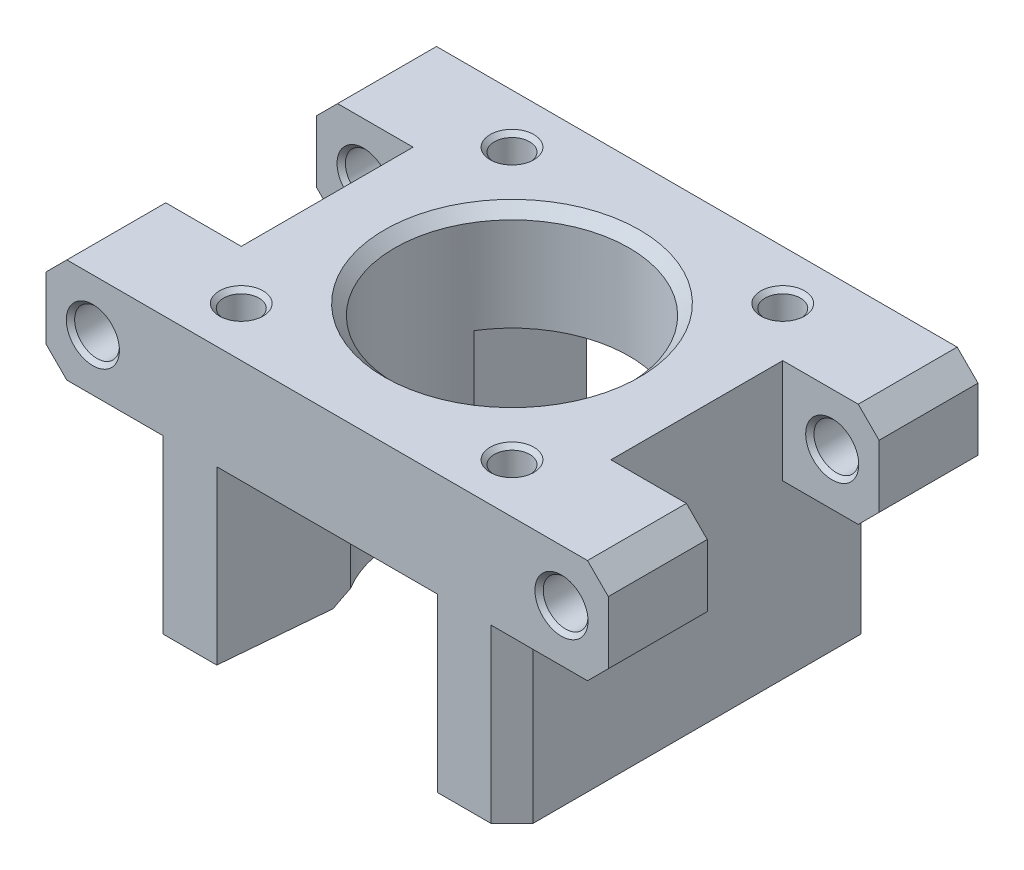
SolidWorks part; units mm, degrees
ref_plane "Top Plane" through (0, 0, 0) normal (0, 0, 1) x (1, 0, 0)
ref_plane "Front Plane" through (0, 0, 0) normal (0, 1, 0) x (1, 0, 0)
ref_plane "Right Plane" through (0, 0, 0) normal (1, 0, 0) x (0, 0, -1)
sketch "Sketch1" plane through (0, 0, 0) normal (0, 0, 1) x (1, 0, 0)
  line L0 (0, 0) -> (0, -10)
  line L1 (0, -10) -> (9.25, -10)
  line L2 (9.25, -10) -> (9.25, -26.5)
  line L3 (9.25, -26.5) -> (44.75, -26.5)
  line L4 (44.75, -26.5) -> (44.75, -10)
  line L5 (44.75, -10) -> (54, -10)
  line L6 (54, -10) -> (54, 0)
  line L7 (54, 0) -> (0, 0)
  dimension "D1" = 54
  dimension "D2" = 10
  dimension "D3" = 16.5
  dimension "D4" = 35.5
  dimension "D5" = 9.25
extrude "Boss-Extrude1" add sketch "Sketch1" along normal blind 35.5
sketch "Sketch2" plane through (0, 0, 35.5) normal (0, 0, 1) x (1, 0, 0)
  line L0 (54, 0) -> (0, 0) construction
  line L1 (0, 0) -> (0, -10) construction
  line L2 (54, -10) -> (54, 0) construction
  circle A0 centre (4.5, -5) radius 2.15
  circle A1 centre (49.5, -5) radius 2.15
  dimension "D1" = 4.3
  dimension "D2" = 4.3
  dimension "D3" = 5
  dimension "D4" = 4.5
  dimension "D5" = 5
  dimension "D6" = 4.5
extrude "Cut-Extrude1" cut sketch "Sketch2" against normal blind 35.5
sketch "Sketch3" plane through (0, -26.5, 0) normal (0, -1, 0) x (1, 0, 0)
  line L0 (9.25, 35.5) -> (9.25, 0) construction
  line L1 (9.25, 0) -> (44.75, 0) construction
  circle A0 centre (27, 17.75) radius 11.25
  dimension "D1" = 22.5
  dimension "D2" = 17.75
  dimension "D3" = 17.75
extrude "Cut-Extrude2" cut sketch "Sketch3" against normal blind 35.5
sketch "Sketch4" plane through (0, -26.5, 0) normal (0, -1, 0) x (1, 0, 0)
  line L1 (40, 4.75) -> (14, 4.75)
  line L2 (40, 4.75) -> (40, 30.75)
  line L3 (40, 30.75) -> (14, 30.75)
  line L4 (14, 4.75) -> (14, 30.75)
  line L5 (40, 4.75) -> (14, 30.75) construction
  line L6 (40, 30.75) -> (14, 4.75) construction
  point P0 (27, 17.75)
  dimension "D1" = 26
  dimension "D2" = 26
hole_wizard "M3 Clearance Hole1" positions "Sketch5" profile "Sketch7" hole size "M3" standard "DIN" end condition through all
sketch "Sketch5" plane through (0, -26.5, 0) normal (0, -1, 0) x (-1, 0, 0)
  point P0 (-14, -30.75)
  point P3 (-40, -30.75)
  point P6 (-40, -4.75)
  point P9 (-14, -4.75)
sketch "Sketch7" plane through (14, -26.5, 30.75) normal (1, 0, 0) x (0, 0, -1)
  line L0 (0, 0) -> (0, 26.5)
  line L1 (0, 26.5) -> (1.7, 26.5)
  line L2 (1.7, 26.5) -> (1.7, 0)
  line L5 (1.7, 0) -> (0, 0)
  line L11 (0, -6.35) -> (0, 107.95) construction
  dimension "Thru Hole Dia." = 3.4
  dimension "Thru Hole Depth" = 26.5
sketch "Sketch8" plane through (0, -26.5, 0) normal (0, -1, 0) x (1, 0, 0)
  line L0 (9.25, 35.5) -> (44.75, 35.5) construction
  line L1 (17.5, 35.5) -> (36.5, 35.5)
  line L2 (17.5, 35.5) -> (17.5, 0)
  line L3 (17.5, 0) -> (36.5, 0)
  line L4 (36.5, 35.5) -> (36.5, 0)
  line L5 (9.25, 0) -> (44.75, 0) construction
  circle A0 centre (14, 30.75) radius 1.7 construction
  circle A1 centre (40, 30.75) radius 1.7 construction
  dimension "D1" = 3.5
  dimension "D2" = 3.5
extrude "Cut-Extrude3" cut sketch "Sketch8" against normal up to surface (16.5 mm away) up to face at (4.625, -10, 17.75)
chamfer "Chamfer1" distance 1.1 angle 85 4 edges at (36.5, -18.25, 0) (17.5, -18.25, 0) (36.5, -18.25, 35.5) (17.5, -18.25, 35.5)
sketch "Sketch9" plane through (0, 0, 0) normal (0, 1, 0) x (1, 0, 0)
  line L0 (0, -35.5) -> (0, 0) construction
  line L1 (0, -9.5) -> (9.25, -9.5)
  line L2 (0, -9.5) -> (0, -26)
  line L3 (0, -26) -> (9.25, -26)
  line L4 (9.25, -9.5) -> (9.25, -26)
  line L5 (54, -35.5) -> (54, 0) construction
  line L6 (54, -9.5) -> (44.75, -9.5)
  line L7 (54, -9.5) -> (54, -26)
  line L8 (54, -26) -> (44.75, -26)
  line L9 (44.75, -9.5) -> (44.75, -26)
  line L10 (54, 0) -> (0, 0) construction
  line L11 (54, -35.5) -> (0, -35.5) construction
  dimension "D1" = 9.25
  dimension "D2" = 9.5
  dimension "D3" = 9.5
  dimension "D4" = 9.25
  dimension "D5" = 9.5
  dimension "D6" = 9.5
extrude "Cut-Extrude4" cut sketch "Sketch9" against normal blind 10
chamfer "Chamfer4" distance 2 angle 45 8 edges at (0, 0, 4.75) (0, -10, 4.75) (0, 0, 30.75) (0, -10, 30.75) (54, -10, 4.75) (54, 0, 4.75) (54, -10, 30.75) (54, 0, 30.75)
chamfer "Chamfer6" distance 1 angle 45 3 edges at (27, 0, 6.5) (15.75, -26.5, 17.75) (38.25, -26.5, 17.75)
chamfer "Chamfer7" distance 0.4 angle 45 16 edges at (51.65, -5, 35.5) (51.65, -5, 26) (51.65, -5, 0) (47.35, -5, 9.5) (6.65, -5, 0) (2.35, -5, 9.5) (6.65, -5, 35.5) (6.65, -5, 26) (14, -26.5, 29.05) (14, 0, 29.05) (40, -26.5, 29.05) (40, 0, 29.05) (40, -26.5, 3.05) (40, 0, 3.05) (14, -26.5, 3.05) (14, 0, 3.05)
chamfer "Chamfer8" distance 2 angle 45 4 edges at (44.75, -18.25, 0) (44.75, -18.25, 35.5) (9.25, -18.25, 0) (9.25, -18.25, 35.5)
